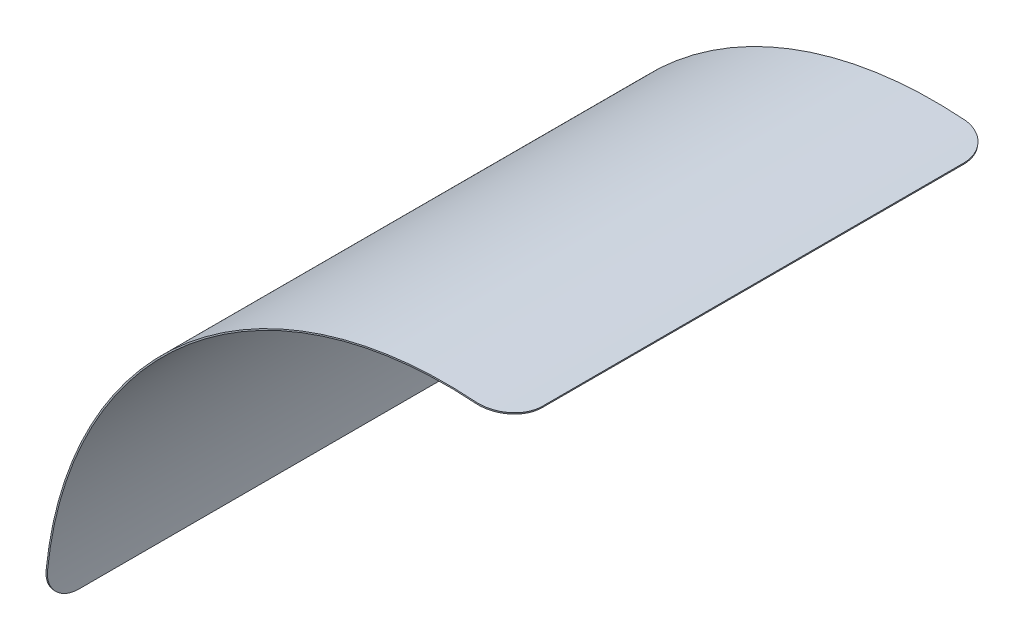
SolidWorks part; units mm, degrees
ref_plane "Front Plane" through (0, 0, 0) normal (0, 0, 1) x (1, 0, 0)
ref_plane "Top Plane" through (0, 0, 0) normal (0, 1, 0) x (1, 0, 0)
ref_plane "Right Plane" through (0, 0, 0) normal (1, 0, 0) x (0, 0, -1)
sketch "Sketch1" plane through (0, 0, 0) normal (0, 0, 1) x (1, 0, 0)
  line L0 (1399.2468, 1174.1075) -> (1398.5522, 1170.1683) construction
  line L1 (0, 0) -> (4, 0) construction
  line L2 (1379.5222, 1177.4151) -> (1378.8938, 1173.4648)
  line L3 (0.1678, 19.9993) -> (4.1672, 19.9322)
  arc A0 (0, 0) -> (1399.2468, 1174.1075) centre (1192.22, 0) cw construction
  arc A1 (4, 0) -> (1398.5522, 1170.1683) centre (1192.22, 0) cw construction
  arc A2 (0.1678, 19.9993) -> (1379.5222, 1177.4151) centre (1192.22, 0) cw
  arc A3 (4.1672, 19.9322) -> (1378.8938, 1173.4648) centre (1192.22, 0) cw
  dimension "D1" = 1192.22
  dimension "D3" = 100
  dimension "D5" = 20
  dimension "D6" = 20
  dimension "D2" = 4
  dimension "D4" = 4
extrude "Boss-Extrude1" add sketch "Sketch1" along normal blind 1450
fillet "Fillet1" radius 100 4 edges at (2.1675, 19.9657, 1450) (2.1675, 19.9657, 0) (1379.208, 1175.44, 0) (1379.208, 1175.44, 1450)
